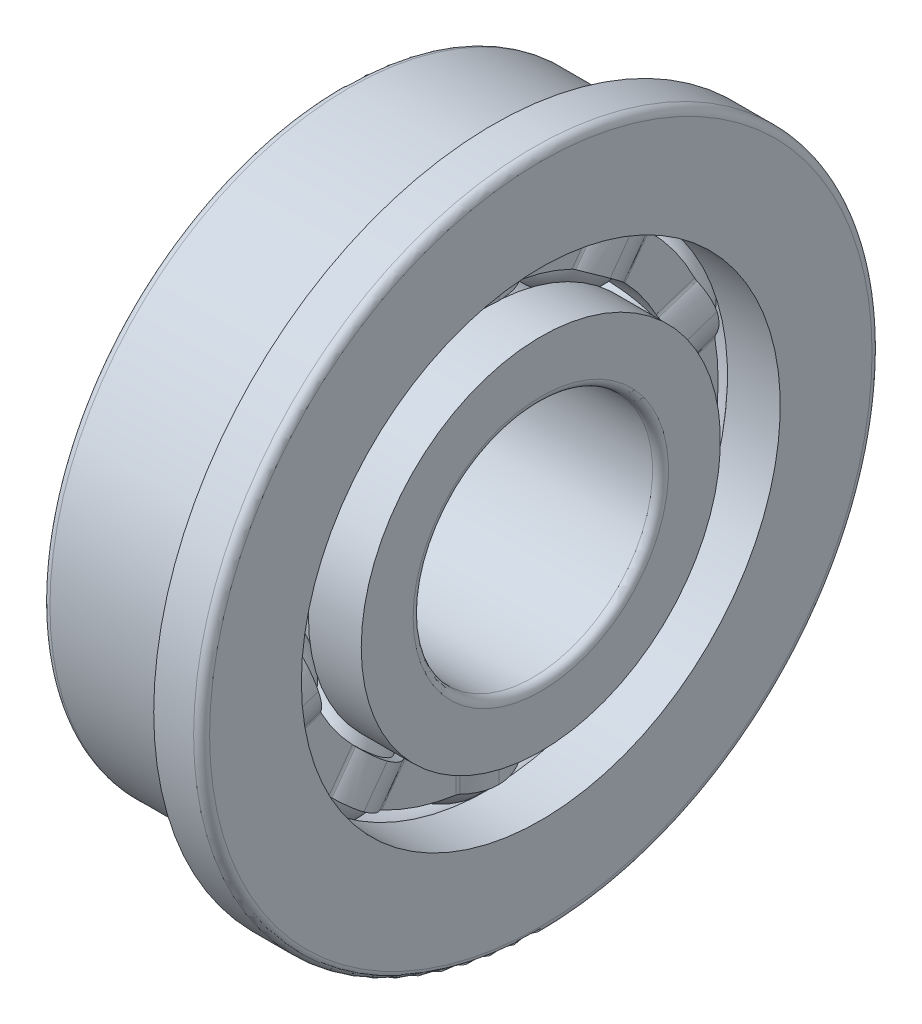
SolidWorks part; units mm, degrees
ref_plane "Front" through (0, 0, 0) normal (0, 0, 1) x (1, 0, 0)
ref_plane "Top" through (0, 0, 0) normal (0, 1, 0) x (1, 0, 0)
ref_plane "Right" through (0, 0, 0) normal (1, 0, 0) x (0, 0, -1)
sketch "Support-Front-Body" plane through (0, 0, 0) normal (0, 0, 1) x (1, 0, 0)
  line L0 (-2.5, 0) -> (2.5, 0) construction
  line L1 (2.5, 0) -> (2.5, 3) construction
  line L2 (-2.5, 0) -> (-2.5, 3) construction
  line L4 (-2.5, 7.5) -> (2.5, 7.5)
  line L5 (-2.5, 7.5) -> (-2.5, 6)
  line L6 (-2.5, 6) -> (2.5, 6)
  line L7 (2.5, 8.5) -> (2.5, 6)
  line L8 (-2.5, 4.5) -> (2.5, 4.5)
  line L9 (-2.5, 4.5) -> (-2.5, 3)
  line L10 (-2.5, 3) -> (2.5, 3)
  line L11 (2.5, 4.5) -> (2.5, 3)
  line L13 (-2.5, 5.25) -> (2.5, 5.25) construction
  line L14 (0, 0) -> (0, 3) construction
  line L15 (0, 3) -> (0, 4.5) construction
  line L16 (0, 4.5) -> (0, 6) construction
  line L17 (0, 6) -> (0, 7.5) construction
  line L19 (1.3, 8.5) -> (2.5, 8.5)
  line L20 (1.3, 8.5) -> (1.3, 7.5)
  dimension "Diam-Inner" = 6
  dimension "Diam-Outer" = 15
  dimension "CC-Ball" = 10.5
  dimension "Width-Inner" = 5
  dimension "Diam-Flange" = 17
  dimension "Width-Flange" = 1.2
sketch "Support-Front-Ball" plane through (0, 0, 0) normal (0, 0, 1) x (1, 0, 0)
  line L0 (-1.35, 5.25) -> (1.35, 5.25) construction
  line L1 (0, 0) -> (0, 3.9) construction
  line L2 (-2.5, 5.25) -> (2.5, 5.25) construction
  line L3 (0, 5.25) -> (0, 6.6) construction
  line L6 (0, 3.9) -> (0, 5.25) construction
  circle A0 centre (0, 5.25) radius 1.35
  dimension "Diam-Ball" = 2.7
sketch "Support-Front-Groove" plane through (0, 0, 0) normal (0, 0, 1) x (1, 0, 0)
  line L0 (0, 6) -> (0, 5.75) construction
  line L1 (0, 5.75) -> (0, 5.5) construction
  line L2 (0, 5.5) -> (0, 5.25) construction
  line L3 (-2.5, 5.25) -> (2.5, 5.25) construction
  line L4 (-1.35, 5.25) -> (1.35, 5.25) construction
  line L6 (-2.5, 6) -> (2.5, 6) construction
  line L7 (0, 3.9551) -> (0, 3.9) construction
  line L8 (1.1225, 4.5) -> (1.1776, 4.5) construction
  line L9 (-2.5, 4.5) -> (2.5, 4.5) construction
  line L11 (0, 0) -> (0, 3.9) construction
  line L12 (-1.35, 5.25) -> (1.35, 5.25) construction
  circle A0 centre (0, 5.25) radius 1.35 construction
  circle A1 centre (0, 5.5) radius 1.5449
  circle A2 centre (0, 5) radius 1.5449
sketch "Support-Front-Ball-Cage" plane through (0, 0, 0) normal (0, 0, 1) x (1, 0, 0)
  line L0 (1.35, 5.25) -> (-1.4466, 5.25) construction
  line L1 (-1.4466, 5.75) -> (1.4466, 5.75)
  line L2 (-1.4466, 5.75) -> (-1.4466, 4.75)
  line L3 (-1.4466, 4.75) -> (1.4466, 4.75)
  line L4 (1.4466, 5.75) -> (1.4466, 4.75)
  line L5 (-2.5, 5.25) -> (2.5, 5.25) construction
  line L6 (0, 4.75) -> (0, 5.75) construction
  line L7 (0, 4.5) -> (0, 6) construction
  line L8 (1.35, 5.25) -> (1.4466, 5.25) construction
  line L9 (1.3983, 5.25) -> (1.3983, 5.5) construction
  line L10 (1.3983, 5.5) -> (1.3983, 5.75) construction
  line L11 (1.3983, 5.75) -> (1.3983, 6) construction
  line L12 (-2.5, 6) -> (2.5, 6) construction
  line L13 (1.4466, 5.875) -> (1.1966, 5.875) construction
  line L14 (0, 5.75) -> (0, 6.6966) construction
  circle A0 centre (0, 5.25) radius 1.35 construction
  circle A1 centre (0, 5.25) radius 1.4466 construction
  point P26 (1.3983, 5.875)
sketch "Support-Right-Ball-Cage" plane through (0, 0, 0) normal (1, 0, 0) x (0, 0, -1)
  line L0 (0, 0) -> (0, 7.5) construction
  line L1 (0, 0) -> (-4.4084, 6.0676) construction
  line L2 (0, 3.8034) -> (-2.2356, 3.077) construction
  line L3 (-3.9362, 5.4177) -> (0, 6.6966) construction
  line L4 (0, 0) -> (-2.5658, 7.0474) construction
  line L6 (-2.0666, 7.2097) -> (0, 0) construction
  circle A0 centre (0, 0) radius 4.75
  circle A1 centre (0, 0) radius 5.75
  circle A2 centre (0, 5.25) radius 1.4466
  circle A3 centre (0, 0) radius 5.25 construction
  circle A4 centre (-3.0859, 4.2473) radius 1.4466
  dimension "Angle-Ball" = 36
ref_plane "Ref-Plane-1" through (0, 3.4402, 1.1178) normal (0, 0.9511, 0.309) x (-1, 0, 0)
sketch "Support-Ball-Gage-Inner" plane through (0, 3.4402, 1.1178) normal (0, 0.9511, 0.309) x (-1, 0, 0)
  line L0 (-1.1941, -0.3118) -> (-1.1941, 0.3118)
  line L1 (1.1941, -0.3118) -> (1.1941, 0.3118)
  line L2 (1.4466, 1.1753) -> (1.4466, -1.1753)
  line L3 (-1.4466, 0) -> (-1.1941, 0) construction
  line L4 (-1.35, -1.6223) -> (-1.35, -0.3118) construction
  line L5 (-1.35, -0.3118) -> (-1.1941, -0.3118) construction
  line L6 (-1.35, -0.3118) -> (-1.35, -0.1559) construction
  line L7 (-1.35, -0.1559) -> (-1.35, 0) construction
  line L8 (-1.1941, 0) -> (0, 0) construction
  line L9 (-1.4466, 1.1753) -> (-1.4466, -1.1753)
  line L10 (-1.4466, -1.7768) -> (-1.4466, -1.4678) construction
  line L11 (-1.35, -0.1559) -> (-1.1941, -0.3118) construction
  line L12 (0, 1.1753) -> (0, -1.1753) construction
  arc A0 (-1.4466, -1.1753) -> (-1.2187, -0.3958) centre (0, -1.1753) cw
  arc A1 (-1.2187, -0.3958) -> (-1.1941, -0.3118) centre (-1.35, -0.3118) ccw
  arc A2 (-1.1941, 0.3118) -> (-1.2187, 0.3958) centre (-1.35, 0.3118) ccw
  arc A3 (-1.2187, 0.3958) -> (-1.4466, 1.1753) centre (0, 1.1753) cw
  arc A4 (1.2187, 0.3958) -> (1.4466, 1.1753) centre (0, 1.1753) ccw
  arc A5 (1.1941, 0.3118) -> (1.2187, 0.3958) centre (1.35, 0.3118) cw
  arc A6 (1.2187, -0.3958) -> (1.1941, -0.3118) centre (1.35, -0.3118) cw
  arc A7 (1.4466, -1.1753) -> (1.2187, -0.3958) centre (0, -1.1753) ccw
  dimension "D1" = 45
ref_plane "Ref-Plane-2" through (0, 6.0571, 1.9681) normal (0, -0.9511, -0.309) x (1, 0, 0)
sketch "Support-Ball-Gage-Outer" plane through (0, 6.0571, 1.9681) normal (0, -0.9511, -0.309) x (1, 0, 0)
  line L0 (1.4466, 2.0694) -> (1.4466, -2.0694)
  line L1 (1.1941, -1.2059) -> (1.1941, 1.2059)
  line L2 (1.4466, 1.1753) -> (1.4466, -1.1753) construction
  line L7 (1.1941, -0.3118) -> (1.1941, 0.3118) construction
  line L8 (0, 2.0694) -> (0, -2.0694) construction
  line L9 (-1.4466, 2.0694) -> (-1.4466, -2.0694)
  line L10 (-1.1941, -1.2059) -> (-1.1941, 1.2059)
  arc A0 (1.4466, -2.0694) -> (1.2187, -1.2899) centre (0, -2.0694) ccw
  arc A1 (1.2187, -1.2899) -> (1.1941, -1.2059) centre (1.35, -1.2059) cw
  arc A2 (1.1941, 1.2059) -> (1.2187, 1.2899) centre (1.35, 1.2059) cw
  arc A3 (1.2187, 1.2899) -> (1.4466, 2.0694) centre (0, 2.0694) ccw
  arc A4 (1.2187, 0.3958) -> (1.1941, 0.3118) centre (1.35, 0.3118) ccw construction
  arc A5 (-1.2187, -1.2899) -> (-1.1941, -1.2059) centre (-1.35, -1.2059) ccw
  arc A6 (-1.4466, -2.0694) -> (-1.2187, -1.2899) centre (0, -2.0694) cw
  arc A7 (-1.2187, 1.2899) -> (-1.4466, 2.0694) centre (0, 2.0694) cw
  arc A8 (-1.1941, 1.2059) -> (-1.2187, 1.2899) centre (-1.35, 1.2059) ccw
ref_axis "Ref-Axis" through (-1.1, 0, 0) along (1, 0, 0)
ref_plane "Ref-Plane-Right" through (2.5, 0, 0) normal (1, 0, 0) x (0, 0, -1)
ref_plane "Ref-Plane-Left" through (-2.5, 0, 0) normal (1, 0, 0) x (0, 0, -1)
sketch "Sketch7" plane through (0, 0, 0) normal (0, 0, 1) x (1, 0, 0)
  line L0 (-1.35, 5.25) -> (1.35, 5.25) construction
  line L2 (-1.35, 5.25) -> (1.35, 5.25) construction
  line L4 (-1.35, 5.25) -> (1.35, 5.25)
  circle A0 centre (0, 5.25) radius 1.35 construction
  arc A1 (-1.35, 5.25) -> (1.35, 5.25) centre (0, 5.25) ccw
revolve "Body-Ball" add sketch "Sketch7" angle 360 about L2
sketch "Sketch10" plane through (0, 0, 0) normal (0, 0, 1) x (1, 0, 0)
  line L0 (-2.5, 0) -> (2.5, 0) construction
  line L1 (-1.4466, 5.75) -> (-1.4466, 4.75) construction
  line L2 (-1.4466, 5.75) -> (1.4466, 5.75) construction
  line L3 (1.4466, 5.75) -> (1.4466, 4.75) construction
  line L4 (-1.4466, 4.75) -> (1.4466, 4.75) construction
  line L5 (-2.5, 0) -> (2.5, 0) construction
  line L6 (-1.4466, 5.75) -> (-1.4466, 4.75)
  line L7 (-1.4466, 5.75) -> (1.4466, 5.75)
  line L8 (1.4466, 5.75) -> (1.4466, 4.75)
  line L9 (-1.4466, 4.75) -> (1.4466, 4.75)
revolve "Body-Ball-Cage" add sketch "Sketch10" angle 360 about L5
sketch "Sketch16" plane through (0, 3.4402, 1.1178) normal (0, 0.9511, 0.309) x (-1, 0, 0)
  line L0 (1.1941, -0.3118) -> (1.1941, 0.3118) construction
  line L1 (1.4466, 1.1753) -> (1.4466, -1.1753) construction
  line L2 (1.1941, -0.3118) -> (1.1941, 0.3118)
  line L3 (1.4466, 1.1753) -> (1.4466, -1.1753)
  arc A0 (1.2187, 0.3958) -> (1.4466, 1.1753) centre (0, 1.1753) ccw construction
  arc A1 (1.2187, 0.3958) -> (1.1941, 0.3118) centre (1.35, 0.3118) ccw construction
  arc A2 (1.1941, -0.3118) -> (1.2187, -0.3958) centre (1.35, -0.3118) ccw construction
  arc A3 (1.4466, -1.1753) -> (1.2187, -0.3958) centre (0, -1.1753) ccw construction
  arc A4 (1.2187, 0.3958) -> (1.4466, 1.1753) centre (0, 1.1753) ccw
  arc A5 (1.2187, 0.3958) -> (1.1941, 0.3118) centre (1.35, 0.3118) ccw
  arc A6 (1.1941, -0.3118) -> (1.2187, -0.3958) centre (1.35, -0.3118) ccw
  arc A7 (1.4466, -1.1753) -> (1.2187, -0.3958) centre (0, -1.1753) ccw
sketch "Sketch17" plane through (0, 6.0571, 1.9681) normal (0, -0.9511, -0.309) x (1, 0, 0)
  line L0 (-1.1941, -1.2059) -> (-1.1941, 1.2059) construction
  line L1 (-1.4466, 2.0694) -> (-1.4466, -2.0694) construction
  line L2 (-1.1941, -1.2059) -> (-1.1941, 1.2059)
  line L3 (-1.4466, 2.0694) -> (-1.4466, -2.0694)
  arc A0 (-1.4466, 2.0694) -> (-1.2187, 1.2899) centre (0, 2.0694) ccw construction
  arc A1 (-1.1941, 1.2059) -> (-1.2187, 1.2899) centre (-1.35, 1.2059) ccw construction
  arc A2 (-1.2187, -1.2899) -> (-1.1941, -1.2059) centre (-1.35, -1.2059) ccw construction
  arc A3 (-1.2187, -1.2899) -> (-1.4466, -2.0694) centre (0, -2.0694) ccw construction
  arc A4 (-1.4466, 2.0694) -> (-1.2187, 1.2899) centre (0, 2.0694) ccw
  arc A5 (-1.1941, 1.2059) -> (-1.2187, 1.2899) centre (-1.35, 1.2059) ccw
  arc A6 (-1.2187, -1.2899) -> (-1.1941, -1.2059) centre (-1.35, -1.2059) ccw
  arc A7 (-1.2187, -1.2899) -> (-1.4466, -2.0694) centre (0, -2.0694) ccw
loft "Cut-Ball-Cage-1" cut profiles "Sketch16", "Sketch17"
sketch "Sketch14" plane through (0, 3.4402, 1.1178) normal (0, 0.9511, 0.309) x (-1, 0, 0)
  line L0 (-1.1941, -0.3118) -> (-1.1941, 0.3118) construction
  line L1 (-1.4466, 1.1753) -> (-1.4466, -1.1753) construction
  line L2 (-1.1941, -0.3118) -> (-1.1941, 0.3118)
  line L3 (-1.4466, 1.1753) -> (-1.4466, -1.1753)
  arc A0 (-1.4466, 1.1753) -> (-1.2187, 0.3958) centre (0, 1.1753) ccw construction
  arc A1 (-1.1941, 0.3118) -> (-1.2187, 0.3958) centre (-1.35, 0.3118) ccw construction
  arc A2 (-1.2187, -0.3958) -> (-1.1941, -0.3118) centre (-1.35, -0.3118) ccw construction
  arc A3 (-1.2187, -0.3958) -> (-1.4466, -1.1753) centre (0, -1.1753) ccw construction
  arc A4 (-1.4466, 1.1753) -> (-1.2187, 0.3958) centre (0, 1.1753) ccw
  arc A5 (-1.1941, 0.3118) -> (-1.2187, 0.3958) centre (-1.35, 0.3118) ccw
  arc A6 (-1.2187, -0.3958) -> (-1.1941, -0.3118) centre (-1.35, -0.3118) ccw
  arc A7 (-1.2187, -0.3958) -> (-1.4466, -1.1753) centre (0, -1.1753) ccw
sketch "Sketch15" plane through (0, 6.0571, 1.9681) normal (0, -0.9511, -0.309) x (1, 0, 0)
  line L0 (1.1941, -1.2059) -> (1.1941, 1.2059) construction
  line L1 (1.4466, 2.0694) -> (1.4466, -2.0694) construction
  line L2 (1.1941, -1.2059) -> (1.1941, 1.2059)
  line L3 (1.4466, 2.0694) -> (1.4466, -2.0694)
  arc A0 (1.2187, 1.2899) -> (1.4466, 2.0694) centre (0, 2.0694) ccw construction
  arc A1 (1.2187, 1.2899) -> (1.1941, 1.2059) centre (1.35, 1.2059) ccw construction
  arc A2 (1.1941, -1.2059) -> (1.2187, -1.2899) centre (1.35, -1.2059) ccw construction
  arc A3 (1.4466, -2.0694) -> (1.2187, -1.2899) centre (0, -2.0694) ccw construction
  arc A4 (1.2187, 1.2899) -> (1.4466, 2.0694) centre (0, 2.0694) ccw
  arc A5 (1.2187, 1.2899) -> (1.1941, 1.2059) centre (1.35, 1.2059) ccw
  arc A6 (1.1941, -1.2059) -> (1.2187, -1.2899) centre (1.35, -1.2059) ccw
  arc A7 (1.4466, -2.0694) -> (1.2187, -1.2899) centre (0, -2.0694) ccw
loft "Cut-Ball-Cage-2" cut profiles "Sketch15", "Sketch14"
pattern_circular "Pattern-Ball" count 10 over 360 about axis through (-1.1, 0, 0) along (1, 0, 0) of "Body-Ball", "Cut-Ball-Cage-2", "Cut-Ball-Cage-1"
sketch "Sketch2" plane through (0, 0, 0) normal (0, 0, 1) x (1, 0, 0)
  line L4 (-2.5, 4.5) -> (-2.5, 3) construction
  line L5 (-2.5, 4.5) -> (2.5, 4.5) construction
  line L6 (2.5, 4.5) -> (2.5, 3) construction
  line L7 (-2.5, 3) -> (2.5, 3) construction
  line L8 (-2.5, 0) -> (2.5, 0) construction
  line L9 (-2.5, 0) -> (2.5, 0) construction
  line L10 (-2.5, 4.5) -> (-2.5, 3)
  line L11 (-2.5, 4.5) -> (-1.1776, 4.5)
  line L12 (2.5, 4.5) -> (2.5, 3)
  line L13 (-2.5, 3) -> (2.5, 3)
  line L14 (1.1776, 4.5) -> (2.5, 4.5)
  circle A1 centre (0, 5.5) radius 1.5449 construction
  arc A2 (-1.1776, 4.5) -> (1.1776, 4.5) centre (0, 5.5) ccw
sketch "Sketch8" plane through (0, 0, 0) normal (0, 0, 1) x (1, 0, 0)
  line L0 (-2.5, 0) -> (2.5, 0) construction
  line L1 (-2.5, 7.5) -> (-2.5, 6) construction
  line L2 (-2.5, 6) -> (2.5, 6) construction
  line L4 (-2.5, 0) -> (2.5, 0) construction
  line L5 (1.3, 8.5) -> (1.3, 7.5) construction
  line L6 (1.3, 8.5) -> (2.5, 8.5) construction
  line L8 (1.3, 8.5) -> (1.3, 7.5)
  line L10 (-2.5, 7.5) -> (-2.5, 6)
  line L11 (-2.5, 6) -> (-1.1776, 6)
  line L12 (2.5, 8.5) -> (2.5, 6) construction
  line L13 (-2.5, 7.5) -> (2.5, 7.5) construction
  line L14 (1.1776, 6) -> (2.5, 6)
  line L15 (1.3, 8.5) -> (2.5, 8.5)
  line L16 (2.5, 8.5) -> (2.5, 6)
  line L17 (-2.5, 7.5) -> (1.3, 7.5)
  circle A1 centre (0, 5) radius 1.5449 construction
  arc A2 (1.1776, 6) -> (-1.1776, 6) centre (0, 5) ccw
revolve "Body-Inner" add sketch "Sketch2" angle 360 about L9
revolve "Body-Outer" add sketch "Sketch8" angle 360 about L4
fillet "Cosmetic-Fillet-Outer-1" radius 0.2 1 edges at (-2.5, 0, 7.5)
fillet "Cosmetic-Fillet-Outer-2" radius 0.2 1 edges at (2.5, 0, 8.5)
fillet "Cosmetic-Fillet-Inner-1" radius 0.2 1 edges at (-2.5, 0, 3)
fillet "Cosmetic-Fillet-Inner-2" radius 0.2 1 edges at (2.5, 0, 3)
equation "\"Diam-Ball@Support-Front-Ball\"=(((\"Diam-Outer@Support-Front-Body\"-\"Diam-Inner@Support-Front-Body\")/2)*3)/5"
equation "\"Num-Ball@Pattern-Ball\"=INT((PI*(\"Diam-Outer@Support-Front-Body\"-((\"Diam-Outer@Support-Front-Body\"-\"Diam-Inner@Support-Front-Body\")/2)))/(\"Diam-Ball@Support-Front-Ball\"*1.2))"
equation "\"Angle-Ball@Support-Right-Ball-Cage\" = 360 / INT(((PI*(\"Diam-Outer@Support-Front-Body\"-((\"Diam-Outer@Support-Front-Body\"-\"Diam-Inner@Support-Front-Body\")/4)))/2)/\"Diam-Ball@Support-Front-Ball\")"
equation "\"Angle-Ball@Support-Right-Ball-Cage\" = 360 / \"Num-Ball@Pattern-Ball\""
